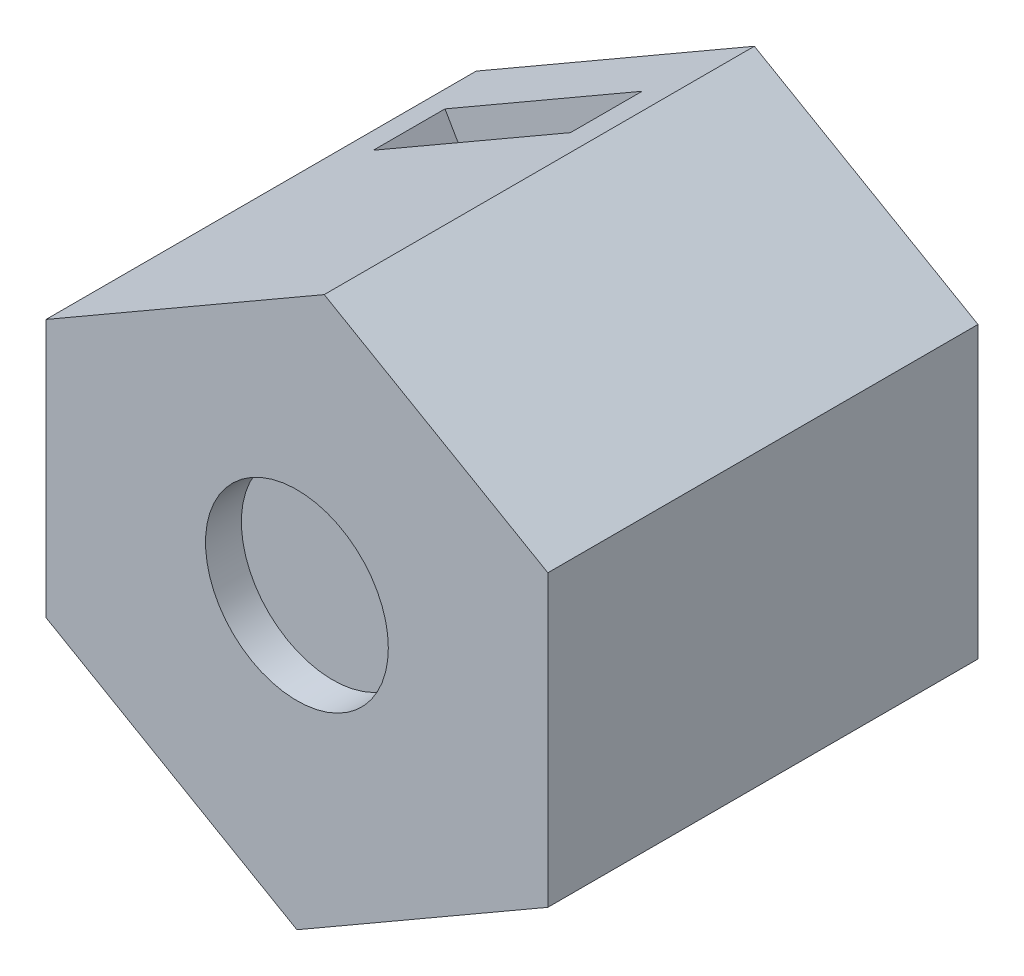
SolidWorks part; units mm, degrees
ref_plane "Front Plane" through (0, 0, 0) normal (0, 0, 1) x (1, 0, 0)
ref_plane "Top Plane" through (0, 0, 0) normal (0, 1, 0) x (1, 0, 0)
ref_plane "Right Plane" through (0, 0, 0) normal (1, 0, 0) x (0, 0, -1)
sketch "Sketch1" plane through (0, 0, 0) normal (0, 0, 1) x (1, 0, 0)
  circle A0 centre (0, 0) radius 7
  dimension "D1" = 14
extrude "Boss-Extrude1" add sketch "Sketch1" along normal blind 12
sketch "Sketch2" plane through (0, 0, 12) normal (0, 0, 1) x (1, 0, 0)
  circle A0 centre (0, 0) radius 2.55
  dimension "D1" = 5.1
extrude "Cut-Extrude1" cut sketch "Sketch2" against normal blind 1
sketch "Sketch3" plane through (0, 0, 0) normal (0, 0, -1) x (-1, 0, 0)
  circle A0 centre (0, 0) radius 1.5
  dimension "D1" = 3
extrude "Cut-Extrude2" cut sketch "Sketch3" against normal blind 4
sketch "Sketch4" plane through (0, 0, 4) normal (0, 0, -1) x (-1, 0, 0)
  line L1 (0, 3.1754) -> (-2.75, 1.5877)
  line L2 (-2.75, 1.5877) -> (-2.75, -1.5877)
  line L3 (-2.75, -1.5877) -> (0, -3.1754)
  line L4 (0, -3.1754) -> (2.75, -1.5877)
  line L5 (2.75, -1.5877) -> (2.75, 1.5877)
  line L6 (2.75, 1.5877) -> (0, 3.1754)
  circle A0 centre (0, 0) radius 2.75 construction
  dimension "D1" = 5.5
extrude "Cut-Extrude3" cut sketch "Sketch4" along normal blind 2
sketch "Sketch5" plane through (-1.375, 2.3816, 0) normal (0.5, -0.866, 0) x (0.866, 0.5, 0)
  line L1 (-3.1754, 4) -> (3.1754, 4)
  line L2 (-3.1754, 4) -> (-3.1754, 2)
  line L3 (-3.1754, 2) -> (3.1754, 2)
  line L4 (3.1754, 4) -> (3.1754, 2)
extrude "Cut-Extrude4" cut sketch "Sketch5" against normal blind 5
extrude "Cut-Extrude5" cut sketch "Sketch5<2>" along normal blind 2.7
sketch "Sketch5<2>" plane through (-1.375, 2.3816, 0) normal (0.5, -0.866, 0) x (0.866, 0.5, 0) same geometry as "Sketch5"
sketch "Sketch6" plane through (0, 0, 0) normal (0, 0, -1) x (-1, 0, 0)
  circle A0 centre (0, 0) radius 1.5
extrude "Cut-Extrude6" cut sketch "Sketch6" against normal blind 7
sketch "Sketch7" plane through (0, 0, 12) normal (0, 0, 1) x (1, 0, 0)
  line L2 (-0.3692, 6.9903) -> (2.725, 1.631)
  line L3 (-0.3692, 6.9903) -> (2.725, 1.631)
  line L4 (-2.775, -1.5444) -> (2.725, 1.631) construction
  line L5 (-5.8692, 3.8148) -> (-2.775, -1.5444)
  line L6 (-5.8692, 3.8148) -> (-2.775, -1.5444)
  line L7 (0, 8.0829) -> (-7, 4.0415)
  line L8 (-7, 4.0415) -> (-7, -4.0415)
  line L9 (-7, -4.0415) -> (0, -8.0829)
  line L10 (0, -8.0829) -> (7, -4.0415)
  line L11 (7, -4.0415) -> (7, 4.0415)
  line L12 (7, 4.0415) -> (0, 8.0829)
  line L13 (-5.8692, 3.8148) -> (-6.25, 4.4745)
  line L14 (-0.3692, 6.9903) -> (-0.75, 7.6499)
  line L15 (-5.8692, 3.8148) -> (-0.3692, 6.9903)
  circle A0 centre (0, 0) radius 7 construction
  circle A1 centre (0, 0) radius 7 construction
  circle A2 centre (0, 0) radius 7
  circle M12 centre (0, 0) radius 7
  dimension "D1" = 0
  dimension "D2" = 0
extrude "Boss-Extrude2" add sketch "Sketch7" against normal up to surface (12 mm away) contours L13 L7 L8 M12 | L14 L12 L7 M12 | L11 L12 M12 | L10 L11 M12 | L9 L10 M12 | L8 L9 M12 region at (0.5619, 7.309, 12) region at (6.2656, 3.6175, 12) region at (6.2656, -3.6175, 12) region at (-6.6107, 3.1678, 12) region at (0, -7.2349, 12) region at (-6.2656, -3.6175, 12) up to face at (-1.5, 0, 0)
extrude "Cut-Extrude7" cut sketch "Sketch7<4>" against normal up to surface (12 mm away) contours L15 M12 region at (-3.2722, 5.6677, 12) up to face at (-1.5, 0, 0)
sketch "Sketch7<4>" plane through (0, 0, 12) normal (0, 0, 1) x (1, 0, 0) same geometry as "Sketch7"
sketch "Sketch8" plane through (0, 0, 12) normal (0, 0, 1) x (1, 0, 0)
  line L0 (-7.004, 3.1596) -> (0.7617, 7.6431)
  line L2 (7, 4.0415) -> (0, 8.0829) construction
  line L3 (-5.8692, 3.8148) -> (-0.3692, 6.9903) construction
  line L24 (-0.3692, 6.9903) -> (-5.8692, 3.8148)
  line L25 (-5.8692, 3.8148) -> (-6.25, 4.4745)
  line L26 (-6.25, 4.4745) -> (-7, 4.0415)
  line L27 (-7, 4.0415) -> (-7, -4.0415)
  line L28 (-7, -4.0415) -> (0, -8.0829)
  line L29 (0, -8.0829) -> (7, -4.0415)
  line L30 (7, -4.0415) -> (7, 4.0415)
  line L31 (7, 4.0415) -> (0, 8.0829)
  line L32 (0, 8.0829) -> (-0.75, 7.6499)
  line L33 (-0.75, 7.6499) -> (-0.3692, 6.9903)
  line L34 (-0.3692, 6.9903) -> (-5.8692, 3.8148)
  line L35 (-5.8692, 3.8148) -> (-6.25, 4.4745)
  line L36 (-6.25, 4.4745) -> (-7, 4.0415)
  line L37 (-7, 4.0415) -> (-7, -4.0415)
  line L38 (-7, -4.0415) -> (0, -8.0829)
  line L39 (0, -8.0829) -> (7, -4.0415)
  line L40 (7, -4.0415) -> (7, 4.0415)
  line L41 (7, 4.0415) -> (0, 8.0829)
  line L42 (0, 8.0829) -> (-0.75, 7.6499)
  line L43 (-0.75, 7.6499) -> (-0.3692, 6.9903)
  point P0 (1.0528, 7.4751)
  point P3 (-3.1212, 5.4014)
  line M13 (-5.8692, 3.8148) -> (-6.25, 4.4745)
  line M14 (-6.25, 4.4745) -> (-7, 4.0415)
  line M15 (-7, 4.0415) -> (-7, -4.0415)
  line M19 (7, 4.0415) -> (0, 8.0829)
  line M20 (0, 8.0829) -> (-0.75, 7.6499)
  line M21 (-0.75, 7.6499) -> (-0.3692, 6.9903)
  dimension "D1" = 0
extrude "Cut-Extrude8" cut sketch "Sketch8" against normal up to surface (12 mm away) contours L0 M15 M13 M14 | L0 M21 M19 M20 region at (-6.5234, 3.8472, 12) region at (-0.0701, 7.573, 12) up to face at (-1.5, 0, 0)
